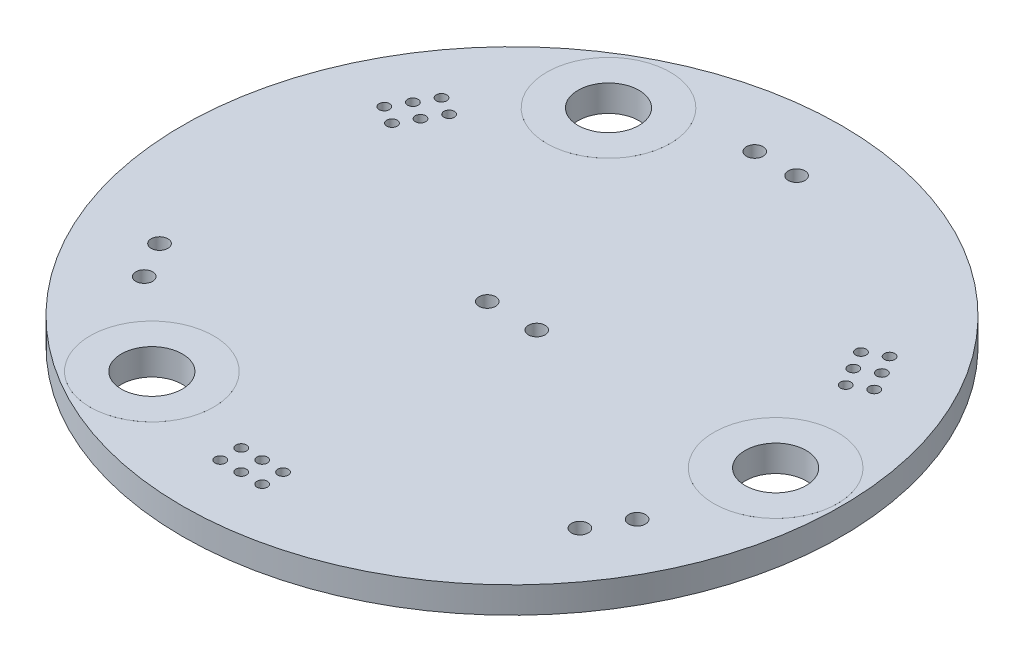
SolidWorks part; units mm, degrees
ref_plane "Front Plane" through (0, 0, 0) normal (0, 0, 1) x (1, 0, 0)
ref_plane "Top Plane" through (0, 0, 0) normal (0, 1, 0) x (1, 0, 0)
ref_plane "Right Plane" through (0, 0, 0) normal (1, 0, 0) x (0, 0, -1)
sketch "Sketch1" plane through (0, 0, 0) normal (0, 1, 0) x (1, 0, 0)
  circle A0 centre (0, 0) radius 20
  dimension "D1" = 40
extrude "Boss-Extrude1" add sketch "Sketch1" along normal blind 1.6
sketch "Sketch2" plane through (0, 1.6, 0) normal (0, 1, 0) x (1, 0, 0)
  line L0 (0, 0) -> (16, 0) construction
  circle A0 centre (16, 0) radius 1.85
  circle A2 centre (-8, -13.8564) radius 1.85
  circle A3 centre (-8, 13.8564) radius 1.85
  point P14 (0, 0)
  dimension "D1" = 16
  dimension "D2" = 3.7
  dimension "D3" = 3
extrude "Cut-Extrude1" cut sketch "Sketch2" against normal through all
ref_axis "Axis1" through (0, 1.6, 0) along (0, -1, 0)
ref_plane "Plane1" through (0, 0, 0) normal (0.866, 0, 0.5) x (0, -1, 0)
sketch "Sketch3" plane through (0, 1.6, 0) normal (0, 1, 0) x (1, 0, 0)
  circle A24 centre (-1.5, 0) radius 0.508
  circle A25 centre (-1.5, 0) radius 0.25 construction
  circle A26 centre (1.5, 0) radius 0.508
  circle A27 centre (1.5, 0) radius 0.25 construction
  circle A43 centre (1.27, 16) radius 0.508
  circle A44 centre (1.27, 16) radius 0.9 construction
  circle A45 centre (-1.27, 16) radius 0.508
  circle A46 centre (-1.27, 16) radius 0.9 construction
  circle A47 centre (13.2214, -9.0999) radius 0.508
  circle A48 centre (14.4914, -6.9001) radius 0.508
  circle A49 centre (-14.4914, -6.9001) radius 0.508
  circle A50 centre (-13.2214, -9.0999) radius 0.508
  circle A51 centre (1.27, -16.4332) radius 0.3175
  circle A52 centre (1.27, -15.1632) radius 0.3175
  circle A53 centre (0, -15.1632) radius 0.3175
  circle A54 centre (-1.27, -15.1632) radius 0.3175
  circle A55 centre (0, -16.4332) radius 0.3175
  circle A56 centre (-1.27, -16.4332) radius 0.3175
  circle A57 centre (-14.8666, 7.1167) radius 0.3175
  circle A58 centre (-13.7667, 6.4817) radius 0.3175
  circle A59 centre (-13.1317, 7.5816) radius 0.3175
  circle A60 centre (-12.4967, 8.6815) radius 0.3175
  circle A61 centre (-14.2316, 8.2166) radius 0.3175
  circle A62 centre (-13.5966, 9.3165) radius 0.3175
  circle A63 centre (13.5966, 9.3165) radius 0.3175
  circle A64 centre (12.4967, 8.6815) radius 0.3175
  circle A65 centre (13.1317, 7.5816) radius 0.3175
  circle A66 centre (13.7667, 6.4817) radius 0.3175
  circle A67 centre (14.2316, 8.2166) radius 0.3175
  circle A68 centre (14.8666, 7.1167) radius 0.3175
  point P4 (11.5546, 12.3931)
  point P6 (-16.51, 3.81)
  point P54 (0, 0)
  point P64 (0, 0)
  point P82 (0, 0)
  dimension "D1" = 0.635
  dimension "D2" = 2
  dimension "D3" = 3
  dimension "D4" = 3
extrude "Cut-Extrude2" cut sketch "Sketch3" against normal through all
sketch "Sketch5" plane through (0, 1.6, 0) normal (0, 1, 0) x (1, 0, 0)
  circle A0 centre (-8, -13.8564) radius 3.75
  circle A1 centre (-8, 13.8564) radius 3.75
  circle A2 centre (16, 0) radius 3.75
  point P3 (0, 0)
  point P4 (0, 0)
  point P9 (0, 0)
  circle M28 centre (16, 0) radius 1.85
  circle M29 centre (-8, -13.8564) radius 1.85
  circle M30 centre (-8, 13.8564) radius 1.85
  dimension "D1" = 7.5
  dimension "D2" = 3
extrude "Boss-Extrude2" add sketch "Sketch5" along normal blind 0.001 contours A0 M29 | A1 M30 | A2 M28 region at (-11.6439, 1.6, 13.8564) region at (-11.6439, 1.6, -13.8564) region at (12.3561, 1.6, 0)
ref_plane "Plane2" through (0, 0.8, 0) normal (0, 1, 0) x (1, 0, 0)
mirror "Mirror1" about plane through (0, 0.8, 0) normal (0, 1, 0) of "Boss-Extrude2"
sketch "Sketch6" plane through (0, 0, 0) normal (0, 1, 0) x (1, 0, 0)
  line L1 (-9.563, 4.0609) -> (9.563, 4.0609) construction
  text T0 "Conn PCB" font "Century Gothic" height 2.5
  point P2 (0, 4.0609)
  point P3 (0, 0)
  point P5 (9.563, 4.0609)
extrude "Boss-Extrude3" add sketch "Sketch6" against normal blind 0.001
sketch "Sketch4" plane through (0, 1.6, 0) normal (0, 1, 0) x (1, 0, 0)
  line L1 (-7.62, -2.71) -> (-7.62, -3.01) construction
  line L2 (-7.62, -3.01) -> (-5.08, -3.01) construction
  line L3 (-5.08, -3.01) -> (-5.08, -2.71) construction
  line L4 (-5.08, -2.71) -> (-7.62, -2.71) construction
  line L5 (7.62, -7.79) -> (7.62, -7.49) construction
  line L6 (7.62, -7.49) -> (5.08, -7.49) construction
  line L7 (5.08, -7.49) -> (5.08, -7.79) construction
  line L8 (5.08, -7.79) -> (7.62, -7.79) construction
  line L9 (-7.62, -2.71) -> (-7.62, -3.01)
  line L10 (-7.62, -3.01) -> (-5.08, -3.01)
  line L11 (-5.08, -3.01) -> (-5.08, -2.71)
  line L12 (-5.08, -2.71) -> (-7.62, -2.71)
  line L13 (7.62, -7.79) -> (7.62, -7.49)
  line L14 (7.62, -7.49) -> (5.08, -7.49)
  line L15 (5.08, -7.49) -> (5.08, -7.79)
  line L16 (5.08, -7.79) -> (7.62, -7.79)
  line L17 (7.62, -7.79) -> (-7.62, -2.71) construction
  point P0 (-8, -13.8564)
  point P1 (-13.2214, -9.0999)
  point P3 (1.27, -15.1632)
  point P5 (-8, 13.8564)
  point P7 (16, 0)
  point P9 (-14.8666, 7.1167)
  point P12 (13.5966, 9.3165)
  point P14 (1.27, -16.4332)
  point P16 (14.4914, -6.9001)
  point P18 (0, -5.25)
  point P19 (-1.27, 16)
  dimension "D1" = 8
  dimension "D2" = 13.8564
  dimension "D3" = 13.8564
  dimension "D4" = 16
  dimension "D5" = 16.4332
  dimension "D6" = 14.8666
  dimension "D7" = 7.1167
  dimension "D8" = 13.5966
  dimension "D9" = 9.3165
  dimension "D10" = 13.2214
  dimension "D11" = 9.0999
  dimension "D12" = 16
  dimension "D13" = 1.27
  dimension "D14" = 6.9001
  dimension "D15" = 14.4914
  dimension "D16" = 5.25
